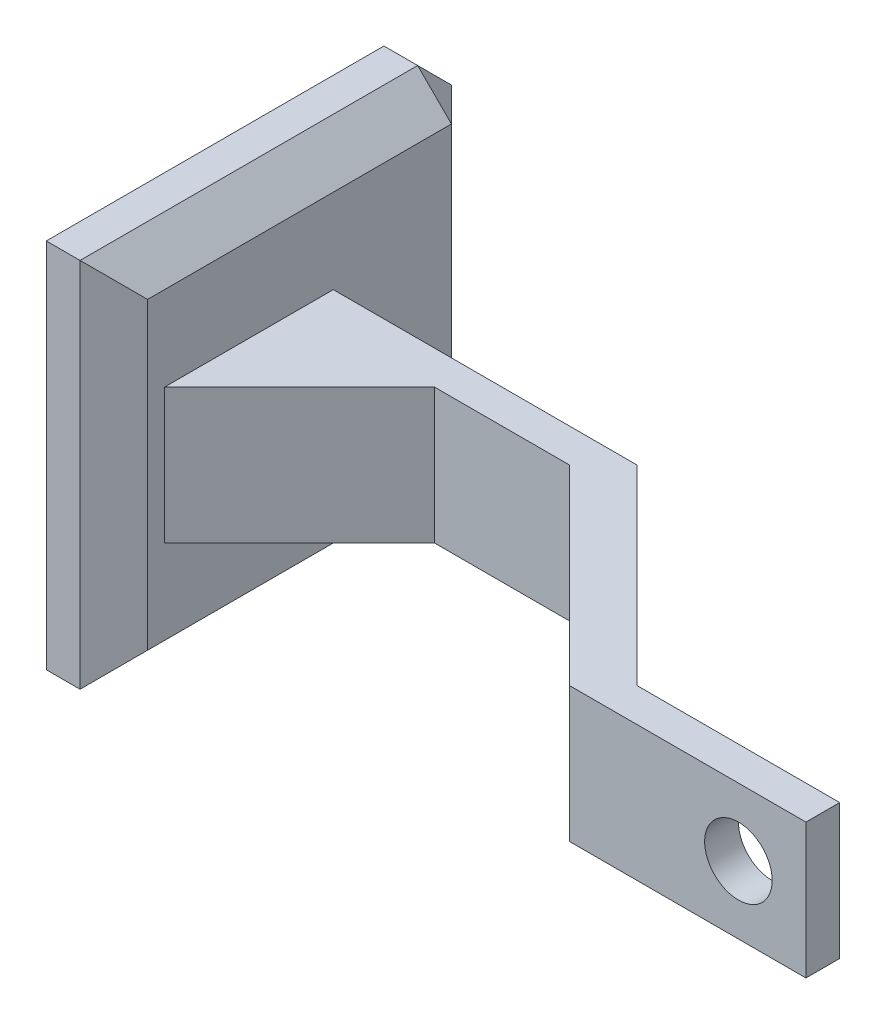
SolidWorks part; units mm, degrees
ref_plane "Front Plane" through (0, 0, 0) normal (0, 0, 1) x (1, 0, 0)
ref_plane "Top Plane" through (0, 0, 0) normal (0, 1, 0) x (1, 0, 0)
ref_plane "Right Plane" through (0, 0, 0) normal (1, 0, 0) x (0, 0, -1)
sketch "Sketch1" plane through (0, 0, 0) normal (0, 0, 1) x (1, 0, 0)
  line L1 (10, 10) -> (-10, 10)
  line L2 (10, 10) -> (10, -10)
  line L3 (10, -10) -> (-10, -10)
  line L4 (-10, 10) -> (-10, -10)
  line L5 (10, 10) -> (-10, -10) construction
  line L6 (10, -10) -> (-10, 10) construction
  circle A0 centre (0, 0) radius 5
  dimension "D1" = 10
  dimension "D2" = 20
  dimension "D3" = 20
extrude "Boss-Extrude1" add sketch "Sketch1" along normal blind 5
sketch "Sketch2" plane through (-10, 0, 0) normal (-1, 0, 0) x (0, 0, 1)
  line L4 (0, 10) -> (0, -10)
  line L5 (0, -10) -> (5, -10)
  line L6 (5, -10) -> (5, 10)
  line L7 (5, 10) -> (0, 10)
  line L8 (0, 10) -> (0, -10)
  line L9 (0, -10) -> (5, -10)
  line L10 (5, -10) -> (5, 10)
  line L11 (5, 10) -> (0, 10)
  dimension "D1" = 0
extrude "Boss-Extrude2" add sketch "Sketch2" along normal blind 15
sketch "Sketch3" plane through (0, -10, 0) normal (0, -1, 0) x (1, 0, 0)
  line L0 (-25, 5) -> (-20, 0)
  line L1 (-25, 5) -> (-53.2843, -23.2843)
  line L2 (-20, 0) -> (-48.2843, -28.2843)
  line L3 (-53.2843, -23.2843) -> (-48.2843, -28.2843)
  line L4 (-25, 0) -> (10, 0) construction
  line L6 (-48.2843, -28.2843) -> (-93.2843, -28.2843)
  line L7 (-48.2843, -28.2843) -> (-48.2843, -23.2843)
  line L8 (-48.2843, -23.2843) -> (-93.2843, -23.2843)
  line L9 (-93.2843, -28.2843) -> (-93.2843, -23.2843)
  line M5 (-25, 0) -> (10, 0)
  line M8 (-25, 5) -> (-25, 0)
  dimension "D1" = 5
  dimension "D2" = 40
  dimension "D3" = 5
  dimension "D4" = 45
extrude "Boss-Extrude3" add sketch "Sketch3" against normal up to surface (20 mm away) contours L8 L7 L2 L1 M5 M8 | L9 L6 L3 L8 | L7 L8 L3 region at (-36.6421, -10, -11.6421) region at (-49.9509, -10, -24.9509) region at (-72.0098, -10, -25.8333) up to face at (-7.5, 10, 2.5)
sketch "Sketch4" plane through (-93.2843, 0, 0) normal (-1, 0, 0) x (0, 0, 1)
  line L0 (-23.2843, 10) -> (-23.2843, -10) construction
  line L1 (4.2157, -27.5) -> (-50.7843, -27.5)
  line L2 (4.2157, -27.5) -> (4.2157, 27.5)
  line L3 (4.2157, 27.5) -> (-50.7843, 27.5)
  line L4 (-50.7843, -27.5) -> (-50.7843, 27.5)
  line L5 (4.2157, -27.5) -> (-50.7843, 27.5) construction
  line L6 (4.2157, 27.5) -> (-50.7843, -27.5) construction
  point P0 (-23.2843, 0)
  dimension "D1" = 55
  dimension "D2" = 55
extrude "Boss-Extrude4" add sketch "Sketch4" along normal blind 10
chamfer "Chamfer1" distance 20 angle 45 1 edges at (-93.2843, 0, -23.2843)
sketch "Sketch5" plane through (-103.2843, 0, 0) normal (-1, 0, 0) x (0, 0, 1)
  line L0 (-50.7843, 0) -> (4.2157, 0) construction
  line L1 (-50.7843, 27.5) -> (-50.7843, -27.5) construction
  line L2 (4.2157, -27.5) -> (4.2157, 27.5) construction
  line L3 (4.2157, 0) -> (-23.2843, 0) construction
  line L4 (-23.2843, 0) -> (-23.2843, 27.5) construction
  line L5 (4.2157, 27.5) -> (-50.7843, 27.5) construction
  line L6 (-37.0343, -13.75) -> (-37.0343, 13.75) construction
  circle A0 centre (-37.0343, -13.75) radius 3.5
  circle A1 centre (-37.0343, 13.75) radius 3.5
  circle A2 centre (-9.5343, -13.75) radius 3.5
  circle A3 centre (-9.5343, 13.75) radius 3.5
  point P10 (-37.0343, 0)
  dimension "D1" = 7
  dimension "D3" = 7
  dimension "D2" = 27.5
  dimension "D4" = 27.5
extrude "Boss-Extrude5" add sketch "Sketch5" along normal blind 10
fillet "Fillet1" radius 2 4 edges at (-113.2843, -13.75, -13.0343) (-113.2843, 13.75, -13.0343) (-113.2843, 13.75, -33.5343) (-113.2843, -13.75, -33.5343)
sketch "Sketch6" plane through (-113.2843, 0, 0) normal (-1, 0, 0) x (0, 0, 1)
  line L0 (-37.0343, -13.75) -> (-9.5343, -13.75) construction
  line L1 (-9.5343, -13.75) -> (-37.0343, 13.75) construction
  line L2 (-37.0343, 13.75) -> (-9.5343, 13.75) construction
  line L5 (-57.5423, 14.25) -> (10.9738, 14.25)
  line L6 (-57.5423, 14.25) -> (-57.5423, 13.25)
  line L7 (-57.5423, 13.25) -> (10.9738, 13.25)
  line L8 (10.9738, 14.25) -> (10.9738, 13.25)
  line L9 (-57.5423, 14.25) -> (10.9738, 13.25) construction
  line L10 (-57.5423, 13.25) -> (10.9738, 14.25) construction
  line L11 (-53.5887, -14.25) -> (7.0202, -14.25)
  line L12 (-53.5887, -14.25) -> (-53.5887, -13.25)
  line L13 (-53.5887, -13.25) -> (7.0202, -13.25)
  line L14 (7.0202, -14.25) -> (7.0202, -13.25)
  line L15 (-53.5887, -14.25) -> (7.0202, -13.25) construction
  line L16 (-53.5887, -13.25) -> (7.0202, -14.25) construction
  circle A3 centre (-9.5343, 13.75) radius 1.5 construction
  circle A4 centre (-37.0343, -13.75) radius 1.5 construction
  circle A5 centre (-37.0343, 13.75) radius 1.5 construction
  point P11 (-23.2843, -13.75)
  point P15 (-23.2843, 13.75)
  dimension "D1" = 1
  dimension "D2" = 1
extrude "Cut-Extrude1" cut sketch "Sketch6" against normal blind 10
sketch "Sketch7" plane through (-103.2843, 0, 0) normal (-1, 0, 0) x (0, 0, 1)
  circle A0 centre (-37.0343, 13.75) radius 3.5
  circle A1 centre (-37.0343, -13.75) radius 3.5
  circle A2 centre (-9.5343, 13.75) radius 3.5
  circle A3 centre (-9.5343, -13.75) radius 3.5
  circle A4 centre (-9.5343, -13.75) radius 3
  circle A5 centre (-37.0343, 13.75) radius 3
  circle A6 centre (-37.0343, -13.75) radius 3
  circle A7 centre (-9.5343, 13.75) radius 3
  dimension "D1" = 0.5
extrude "Cut-Extrude2" cut sketch "Sketch7" along normal blind 6
fillet "Fillet2" radius 2 8 edges at (-109.2843, -10.25, -9.5343) (-109.2843, -17.25, -9.5343) (-109.2843, -17.25, -37.0343) (-109.2843, -10.25, -37.0343) (-109.2843, 17.25, -9.5343) (-109.2843, 10.25, -9.5343) (-109.2843, 17.25, -37.0343) (-109.2843, 10.25, -37.0343)
chamfer "Chamfer2" distance 5 angle 45 7 edges at (-98.2843, 27.5, -50.7843) (-103.2843, 0, -50.7843) (-98.2843, -27.5, -50.7843) (-93.2843, 0, -50.7843) (-93.2843, 27.5, -23.2843) (-93.2843, 0, 4.2157) (-93.2843, -27.5, -23.2843)
